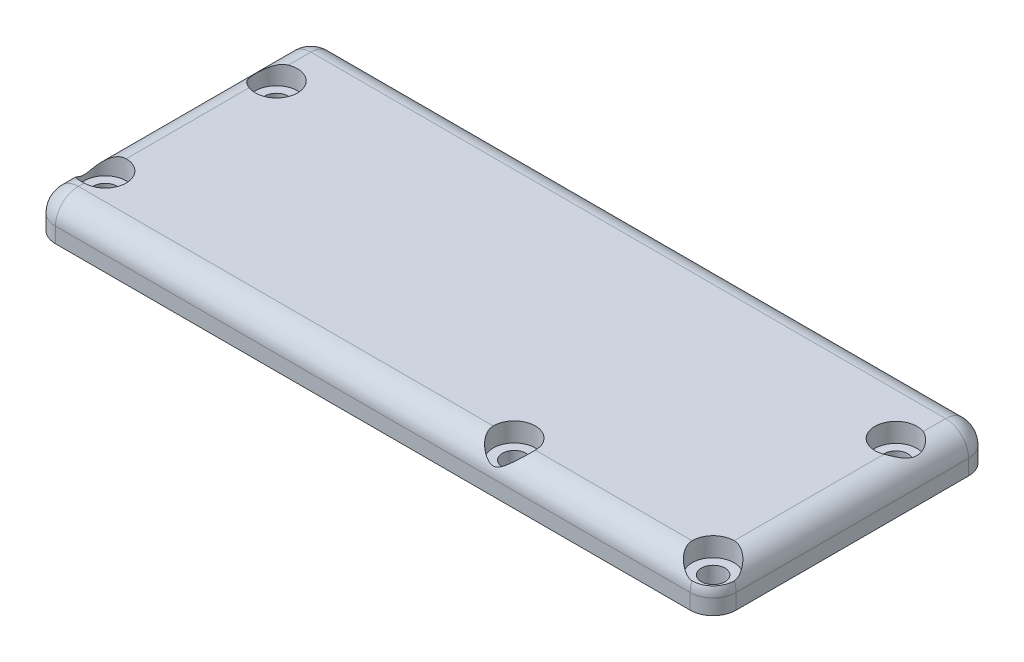
SolidWorks part; units mm, degrees
ref_plane "Front Plane" through (0, 0, 0) normal (0, 0, 1) x (1, 0, 0)
ref_plane "Top Plane" through (0, 0, 0) normal (0, 1, 0) x (1, 0, 0)
ref_plane "Right Plane" through (0, 0, 0) normal (1, 0, 0) x (0, 0, -1)
sketch "Sketch1" plane through (0, 0, 0) normal (0, 1, 0) x (1, 0, 0)
  line L1 (-44.5, -18.2) -> (44.5, -18.2)
  line L2 (-44.5, -18.2) -> (-44.5, 18.2)
  line L3 (-44.5, 18.2) -> (44.5, 18.2)
  line L4 (44.5, -18.2) -> (44.5, 18.2)
  line L5 (-44.5, -18.2) -> (44.5, 18.2) construction
  line L6 (-44.5, 18.2) -> (44.5, -18.2) construction
  point P0 (0, 0)
  dimension "D1" = 89
  dimension "D2" = 36.4
extrude "Boss-Extrude1" add sketch "Sketch1" along normal blind 5
hole_wizard "CBORE for M2.5 SHCS1" positions "Sketch2" profile "Sketch3" counterbore size "M2.5" standard "ANSI Metric" end condition through all
sketch "Sketch2" plane through (0, 5, 0) normal (0, 1, 0) x (1, 0, 0)
  line L0 (-44.5, 18.2) -> (-44.5, -18.2) construction
  line L1 (44.5, -18.2) -> (44.5, 18.2) construction
  line L2 (-44.5, -18.2) -> (44.5, -18.2) construction
  line L3 (44.5, 18.2) -> (-44.5, 18.2) construction
  point P0 (-40.5, 9.7)
  point P2 (-41.5, -11.7)
  point P4 (15.5, -15.2)
  point P6 (41.5, -15.2)
  point P8 (40.5, 9.7)
  dimension "D1" = 3
  dimension "D2" = 3
  dimension "D3" = 3
  dimension "D4" = 6.5
  dimension "D5" = 29
  dimension "D6" = 3
  dimension "D7" = 8.5
  dimension "D8" = 4
  dimension "D9" = 8.5
  dimension "D10" = 4
sketch "Sketch3" plane through (-40.5, 5, -9.7) normal (1, 0, 0) x (0, 0, 1)
  line L0 (0, 0) -> (0, 5)
  line L1 (0, 5) -> (1.55, 5)
  line L3 (1.55, 5) -> (1.55, 2.5)
  line L4 (1.55, 2.5) -> (2.75, 2.5)
  line L5 (2.75, 2.5) -> (2.75, 0)
  line L7 (2.75, 0) -> (0, 0)
  line L11 (0, -6.35) -> (0, 107.95) construction
  dimension "Thru Hole Dia." = 3.1
  dimension "Thru Hole Depth" = 5
  dimension "C'Bore Dia." = 5.5
  dimension "C'Bore Depth" = 2.5
fillet "Fillet3" radius 3 4 edges at (44.5, 2.5, -18.2) (44.5, 2.5, 18.2) (-44.5, 2.5, -18.2) (-44.5, 2.5, 18.2)
fillet "Fillet4" radius 3 7 edges at (-43.6213, 5, -17.3213) (0, 5, -18.2) (43.6213, 5, -17.3213) (44.5, 5, 0) (0, 5, 18.2) (-43.6213, 5, 17.3213) (-44.5, 5, 0)
